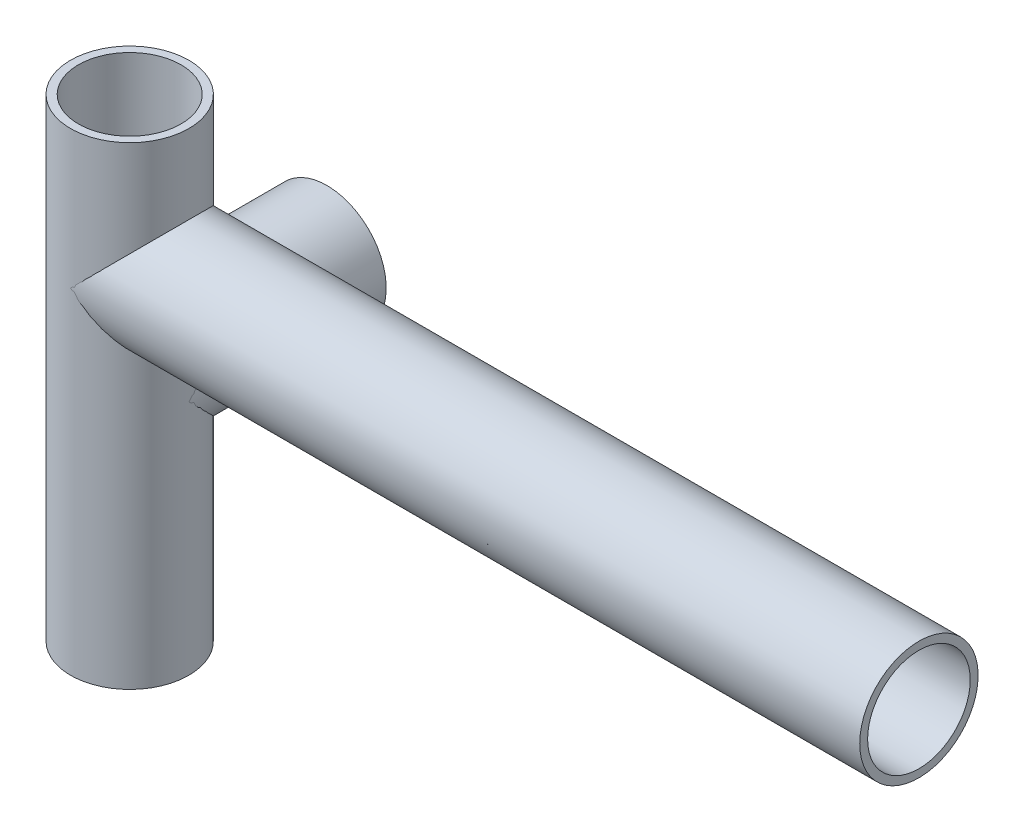
SolidWorks part; units mm, degrees
ref_plane "Front Plane" through (0, 0, 0) normal (0, 0, 1) x (1, 0, 0)
ref_plane "Top Plane" through (0, 0, 0) normal (0, 1, 0) x (1, 0, 0)
ref_plane "Right Plane" through (0, 0, 0) normal (1, 0, 0) x (0, 0, -1)
sketch "Sketch1" plane through (0, 0, 0) normal (1, 0, 0) x (0, 0, -1)
  line L1 (0, 118.3216) -> (0, -1.6784)
  dimension "D2" = 120
sweep "Sweep-Thin6" add path "Sketch1" circular profile diameter 30 parameters "D1"=2, "D3"=30
sketch "Sketch66" plane through (0, 0, 0) normal (1, 0, 0) x (0, 0, -1)
  line L0 (0, 118.3216) -> (0, -1.6784) construction
  line L1 (0, 118.3216) -> (0, -1.6784)
  line L2 (0, 58.3216) -> (50, 58.3216)
  dimension "D1" = 50
sweep "Sweep-Thin8" add path "Sketch66" circular profile diameter 30 parameters "D1"=2, "D3"=30
sketch "Sketch135" plane through (0, 118.3216, 0) normal (0, 1, 0) x (1, 0, 0)
  circle A1 centre (0, 0) radius 15
  circle A2 centre (0, 0) radius 15
  dimension "D1" = 0
extrude "Cut-Extrude1" cut sketch "Sketch135" against normal blind 185
sketch "Sketch142" plane through (0, 0, 0) normal (0, 0, 1) x (1, 0, 0)
  line L0 (0, 58.3216) -> (0, 83.3216)
  line L1 (0, 83.3216) -> (200, 83.3216)
  dimension "D1" = 200
  dimension "D2" = 25
sweep "Sweep-Thin9" add path "Sketch142" circular profile diameter 30 parameters "D1"=2, "D3"=30
sketch "Sketch183" plane through (0, 118.3216, 0) normal (0, 1, 0) x (1, 0, 0)
  circle A0 centre (0, 0) radius 15 construction
  circle A1 centre (0, 0) radius 15
extrude "Cut-Extrude2" cut sketch "Sketch183" against normal through all
